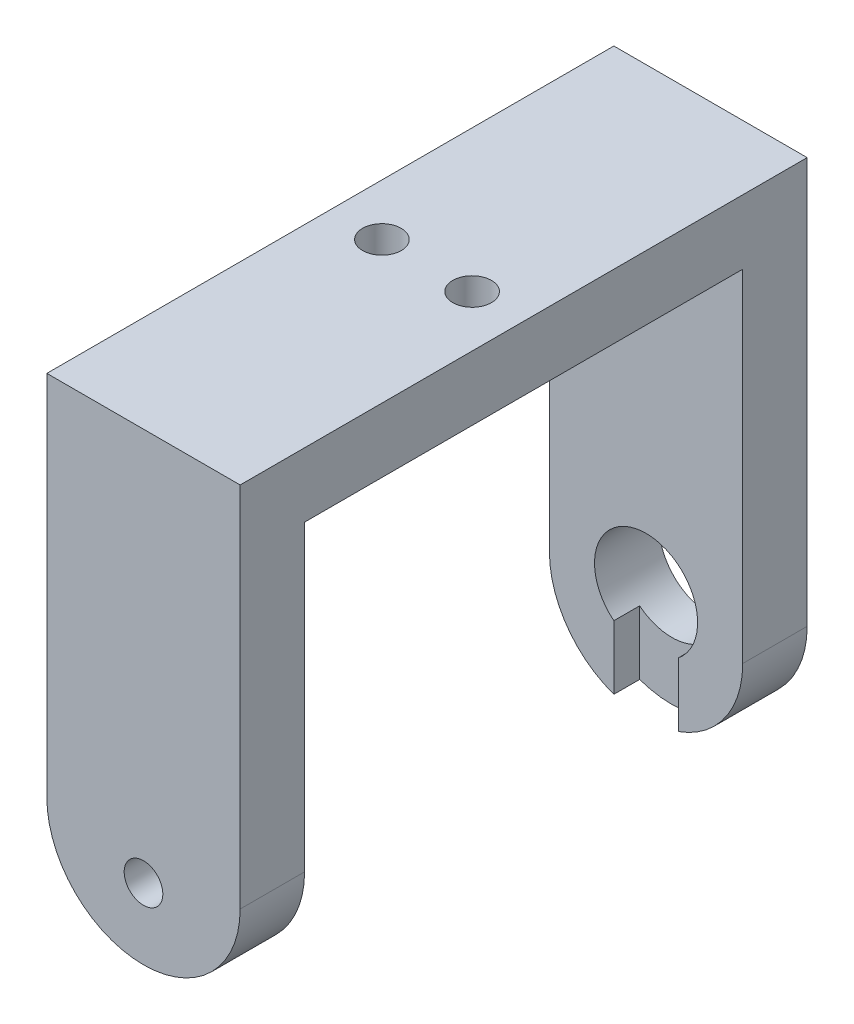
SolidWorks part; units mm, degrees
material "PET"
ref_plane "Alzado" through (0, 0, 0) normal (0, 0, 1) x (1, 0, 0)
ref_plane "Planta" through (0, 0, 0) normal (0, 1, 0) x (1, 0, 0)
ref_plane "Vista lateral" through (0, 0, 0) normal (1, 0, 0) x (0, 0, -1)
sketch "Croquis1" plane through (0, 0, 0) normal (0, 1, 0) x (1, 0, 0)
  line L1 (-7.5, -22) -> (7.5, -22)
  line L2 (-7.5, -22) -> (-7.5, 22)
  line L3 (-7.5, 22) -> (7.5, 22)
  line L4 (7.5, -22) -> (7.5, 22)
  line L5 (-7.5, -22) -> (7.5, 22) construction
  line L6 (-7.5, 22) -> (7.5, -22) construction
  circle A0 centre (3.5, 0) radius 1.5
  circle A1 centre (-3.5, 0) radius 1.5
  point P0 (0, 0)
  dimension "D3" = 3
  dimension "D4" = 4
  dimension "D5" = 7
  dimension "D1" = 15
  dimension "D2" = 44
extrude "Saliente-Extruir1" add sketch "Croquis1" against normal blind 5
sketch "Croquis2" plane through (0, -5, 0) normal (0, -1, 0) x (1, 0, 0)
  line L0 (7.5, 22) -> (7.5, -22) construction
  line L1 (-7.5, 22) -> (7.5, 22)
  line L2 (-7.5, 22) -> (-7.5, 17)
  line L3 (-7.5, 17) -> (7.5, 17)
  line L4 (7.5, 22) -> (7.5, 17)
  line L5 (-7.5, -22) -> (-7.5, 22) construction
  line L6 (7.5, -22) -> (-7.5, -22)
  line L7 (7.5, -22) -> (7.5, -17)
  line L8 (7.5, -17) -> (-7.5, -17)
  line L9 (-7.5, -22) -> (-7.5, -17)
  line M11 (7.5, -22) -> (7.5, 22)
  line M12 (7.5, 22) -> (-7.5, 22)
  line M13 (-7.5, 22) -> (-7.5, -22)
  dimension "D1" = 5
extrude "Saliente-Extruir2" add sketch "Croquis2" along normal blind 34 contours L7 L6 L9 L8
extrude "Saliente-Extruir3" add sketch "Croquis2<3>" along normal blind 31 contours L3 M13 M11 M12 region at (0, -5, 19.5)
sketch "Croquis2<3>" plane through (0, -5, 0) normal (0, -1, 0) x (1, 0, 0) same geometry as "Croquis2"
sketch "Croquis3" plane through (0, 0, 22) normal (0, 0, 1) x (1, 0, 0)
  line L0 (7.5, -36) -> (-7.5, -36) construction
  line L1 (-7.5, -28.5) -> (7.5, -28.5)
  circle A0 centre (0, -30.5) radius 1.5
  arc A1 (-7.5, -28.5) -> (7.5, -28.5) centre (0, -28.5) ccw
  line M5 (-7.5, 0) -> (-7.5, -36)
  line M6 (-7.5, -36) -> (7.5, -36)
  line M7 (7.5, -36) -> (7.5, 0)
  dimension "D1" = 3
  dimension "D3" = 15
  dimension "D2" = 5.5
  dimension "D4" = 7.5
extrude "Cortar-Extruir1" cut sketch "Croquis3" against normal up to next contours A0 | A1 M5 M6 | A1 M6 M7 region at (-5.8247, -34.3247, 22) region at (5.8247, -34.3247, 22) region at (0, -30.5, 22)
sketch "Croquis4" plane through (0, 0, -22) normal (0, 0, -1) x (-1, 0, 0)
  line L0 (-7.5, -39) -> (7.5, -39) construction
  circle A0 centre (0, -30.5) radius 4
  circle A1 centre (0, -31.5) radius 7.5
  line M4 (-7.5, 0) -> (-7.5, -39)
  line M5 (-7.5, -39) -> (7.5, -39)
  line M6 (7.5, -39) -> (7.5, 0)
  dimension "D1" = 8
  dimension "D3" = 15
  dimension "D2" = 8.5
  dimension "D4" = 7.5
extrude "Cortar-Extruir2" cut sketch "Croquis4" against normal up to next contours A0 | A1 M5 M6 | A1 M4 M5 region at (0, -30.5, -22) region at (-5.8247, -37.3247, -22) region at (5.8247, -37.3247, -22)
sketch "Croquis5" plane through (0, 0, -17) normal (0, 0, 1) x (1, 0, 0)
  line L0 (7.5, -5) -> (-7.5, -5) construction
  line L5 (-2.5, -33.6225) -> (2.5, -33.6225)
  line L6 (-2.5, -33.6225) -> (-2.5, -39)
  line L7 (-2.5, -39) -> (2.5, -39)
  line L8 (2.5, -33.6225) -> (2.5, -39)
  circle A0 centre (0, -30.5) radius 4 construction
  arc A1 (-7.5, -31.5) -> (7.5, -31.5) centre (0, -31.5) ccw construction
  point P6 (0, -5)
  point P7 (0, -33.6225)
  point P14 (0, -39)
  point P15 (0, -39)
  dimension "D1" = 5
extrude "Cortar-Extruir3" cut sketch "Croquis5" against normal blind 2
sketch "Croquis6" plane through (0, 0, -22) normal (0, 0, -1) x (-1, 0, 0)
  line L0 (7.5, -26.5) -> (-7.5, -26.5) construction
  line L1 (-3.4641, -10.5) -> (3.4641, -10.5)
  line L2 (-3.4641, -10.5) -> (-3.4641, -28.5)
  line L3 (-3.4641, -28.5) -> (3.4641, -28.5)
  line L4 (3.4641, -10.5) -> (3.4641, -28.5)
  line L5 (-7.5, -31.5) -> (-7.5, 0) construction
  line L6 (-2.125, -10.5) -> (-3.4641, -28.5)
  line L7 (2.125, -10.5) -> (3.4641, -28.5)
  line L8 (-2.125, -10.5) -> (2.125, -10.5) construction
  circle A0 centre (0, -30.5) radius 4 construction
  point P11 (0, -26.5)
  point P13 (0, -10.5)
  circle M6 centre (0, -30.5) radius 4
  dimension "D1" = 2
  dimension "D2" = 18
  dimension "D3" = 4.25
  dimension "D4" = 2.125
extrude "Cortar-Extruir4" cut sketch "Croquis6" against normal blind 3 contours L7 L1 L6 M6 region at (0, -19.4111, -22)
